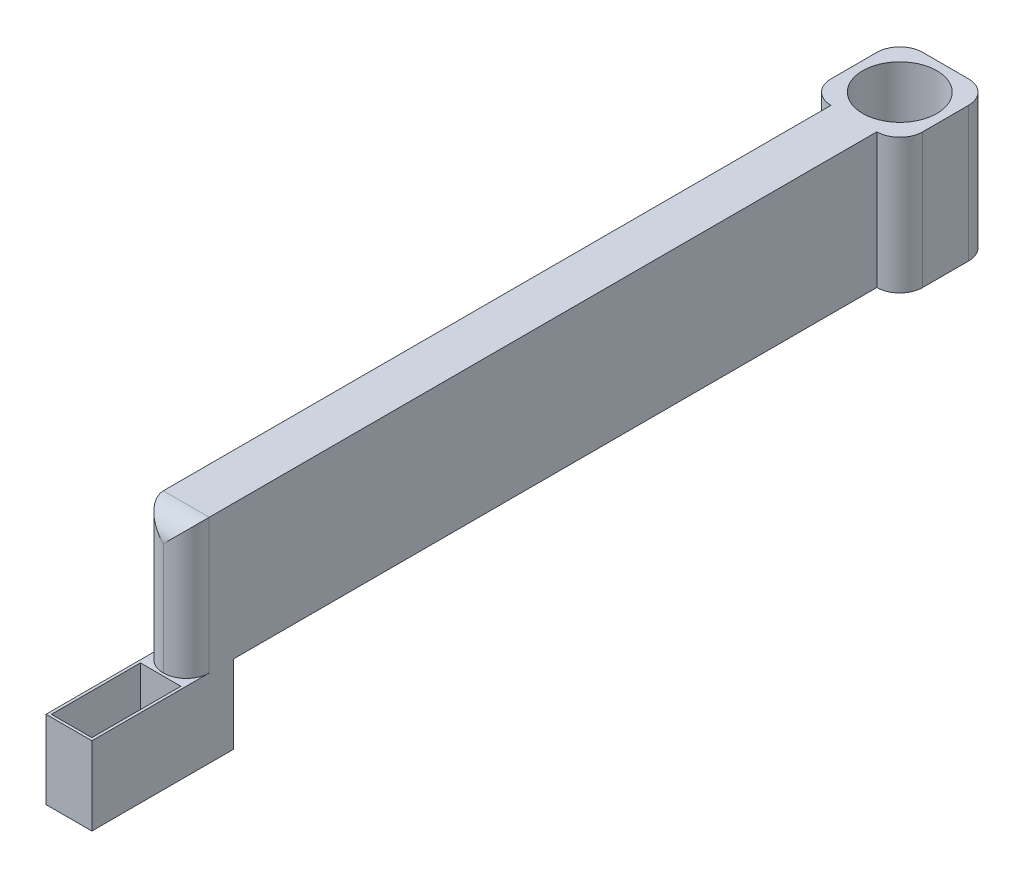
SolidWorks part; units mm, degrees
ref_plane "Front Plane" through (0, 0, 0) normal (0, 0, 1) x (1, 0, 0)
ref_plane "Top Plane" through (0, 0, 0) normal (0, 1, 0) x (1, 0, 0)
ref_plane "Right Plane" through (0, 0, 0) normal (1, 0, 0) x (0, 0, -1)
sketch "Sketch2" plane through (0, 0, 0) normal (0, 1, 0) x (1, 0, 0)
  line L0 (-68, 0) -> (-34, -68) construction
  line L1 (0, 0) -> (-68, 0)
  line L2 (0, 0) -> (0, -68)
  line L3 (0, -68) -> (-68, -68)
  line L4 (-68, 0) -> (-68, -68)
  line L5 (-34, -68) -> (0, 0) construction
  line L6 (-51, -34) -> (-51, -68) construction
  line L7 (-17, -34) -> (-17, -68) construction
  line L8 (-51, -68) -> (-51, -580)
  line L9 (-51, -580) -> (-17, -580)
  line L10 (-17, -580) -> (-17, -68)
  line L11 (-51, -580) -> (-51, -650)
  line L12 (-51, -650) -> (-17, -650)
  line L13 (-17, -650) -> (-17, -580)
  dimension "D1" = 34
  dimension "D2" = 650
  dimension "D3" = 580
  dimension "D4" = 68
extrude "Boss-Extrude1" add sketch "Sketch2" along normal blind 158 contours L9 L10 L3 L8 | L12 L13 L9 L11 | L1 L4 L3 L2 region at (-34, 0, 34) region at (-34, 0, 324) region at (-34, 0, 615)
fillet "Fillet1" radius 17 4 edges at (0, 79, 0) (0, 79, 68) (-68, 79, 0) (-68, 79, 68)
sketch "Sketch3" plane through (-51, 0, 0) normal (-1, 0, 0) x (0, 0, 1)
  line L0 (68, 0) -> (650, 0) construction
  line L1 (545, 0) -> (-54.3739, 0)
  line L2 (545, 0) -> (545, 58)
  line L3 (545, 58) -> (-54.3739, 58)
  line L4 (-54.3739, 0) -> (-54.3739, 58)
  line L5 (650, 158) -> (650, 0) construction
  line L6 (68, 158) -> (650, 158) construction
  dimension "D1" = 105
  dimension "D2" = 100
  dimension "D3" = 704.3739
extrude "Cut-Extrude1" cut sketch "Sketch3" against normal blind 158
sketch "Sketch4" plane through (-51, 0, 0) normal (1, 0, 0) x (0, 0, -1)
  line L1 (-68, 58) -> (0, 58)
  line L2 (-68, 58) -> (-68, 0)
  line L3 (-68, 0) -> (0, 0)
  line L4 (0, 58) -> (0, 0)
extrude "Cut-Extrude2" cut sketch "Sketch4" against normal blind 158
sketch "Sketch5" plane through (0, 158, 0) normal (0, 1, 0) x (1, 0, 0)
  line L0 (-51, -68) -> (-17, -68) construction
  line L1 (-34, 0) -> (-34, -3.2369) construction
  line L2 (-17, 0) -> (-51, 0) construction
  line L3 (-34, 0) -> (-34, -68) construction
  circle A0 centre (-34, -34) radius 27.5
  dimension "D1" = 55
extrude "Cut-Extrude3" cut sketch "Sketch5" against normal blind 158
sketch "Sketch6" plane through (-51, 0, 0) normal (-1, 0, 0) x (0, 0, 1)
  line L0 (650, 158) -> (650, 0) construction
  line L1 (545, 0) -> (650, 0)
  line L2 (545, 0) -> (545, 58)
  line L3 (545, 58) -> (650, 58)
  line L4 (650, 0) -> (650, 58)
  line L6 (650, 158) -> (580, 158)
  line L7 (650, 158) -> (650, 58)
  line L8 (650, 58) -> (580, 58)
  line L9 (580, 158) -> (580, 58)
  line M4 (650, 0) -> (650, 158)
  line M5 (650, 158) -> (68, 158)
  dimension "D1" = 58
  dimension "D2" = 70
  dimension "D3" = 100
extrude "Cut-Extrude4" cut sketch "Sketch6" against normal blind 84 contours L9 L3 M5 M4 region at (-51, 108, 615)
sketch "Sketch7" plane through (0, 58, 0) normal (0, 1, 0) x (1, 0, 0)
  line L0 (-17, -650) -> (-51, -650) construction
  line L1 (-49, -582) -> (-19, -582)
  line L2 (-49, -582) -> (-49, -648)
  line L3 (-49, -648) -> (-19, -648)
  line L4 (-19, -582) -> (-19, -648)
  line L5 (-17, -580) -> (-51, -580) construction
  line L6 (-51, -580) -> (-51, -650) construction
  line L7 (-17, -580) -> (-17, -650) construction
  dimension "D1" = 2
  dimension "D2" = 2
  dimension "D3" = 2
  dimension "D4" = 2
extrude "Cut-Extrude6" cut sketch "Sketch7" against normal blind 56
sketch "Sketch8" plane through (0, 2, 0) normal (0, 1, 0) x (1, 0, 0)
  line L0 (-19, -582) -> (-49, -582) construction
  line L1 (-46, -592) -> (-24, -592)
  line L2 (-46, -592) -> (-46, -605)
  line L3 (-46, -605) -> (-24, -605)
  line L4 (-24, -592) -> (-24, -605)
  line L5 (-17, -650) -> (-51, -650) construction
  line L6 (-51, -580) -> (-51, -650) construction
  line L7 (-19, -648) -> (-19, -582) construction
  dimension "D1" = 10
  dimension "D2" = 45
  dimension "D3" = 5
  dimension "D4" = 5
extrude "Cut-Extrude7" cut sketch "Sketch8" against normal blind 56
fillet "Fillet2" radius 17 3 edges at (-51, 108, 580) (-17, 108, 580) (-34, 158, 580)
sketch "Sketch9" plane through (-17, 0, 0) normal (1, 0, 0) x (0, 0, -1)
  line L0 (-563, 158) -> (-563, 58) construction
  line L1 (-543, 143) -> (-88, 143)
  line L2 (-543, 143) -> (-543, 73)
  line L3 (-543, 73) -> (-88, 73)
  line L4 (-88, 143) -> (-88, 73)
  line L5 (-68, 158) -> (-68, 58) construction
  line L6 (-563, 158) -> (-68, 158) construction
  line L7 (-545, 58) -> (-68, 58) construction
  dimension "D1" = 20
  dimension "D2" = 20
  dimension "D3" = 15
  dimension "D4" = 15
extrude "Cut-Extrude8" cut sketch "Sketch9" against normal blind 111
sketch "Sketch10" plane through (-51, 0, 0) normal (-1, 0, 0) x (0, 0, 1)
  line L1 (78.4607, 64.527) -> (548.9226, 64.527)
  line L2 (78.4607, 64.527) -> (78.4607, 151.3636)
  line L3 (78.4607, 151.3636) -> (548.9226, 151.3636)
  line L4 (548.9226, 64.527) -> (548.9226, 151.3636)
extrude "Boss-Extrude3" add sketch "Sketch10" against normal blind 34
